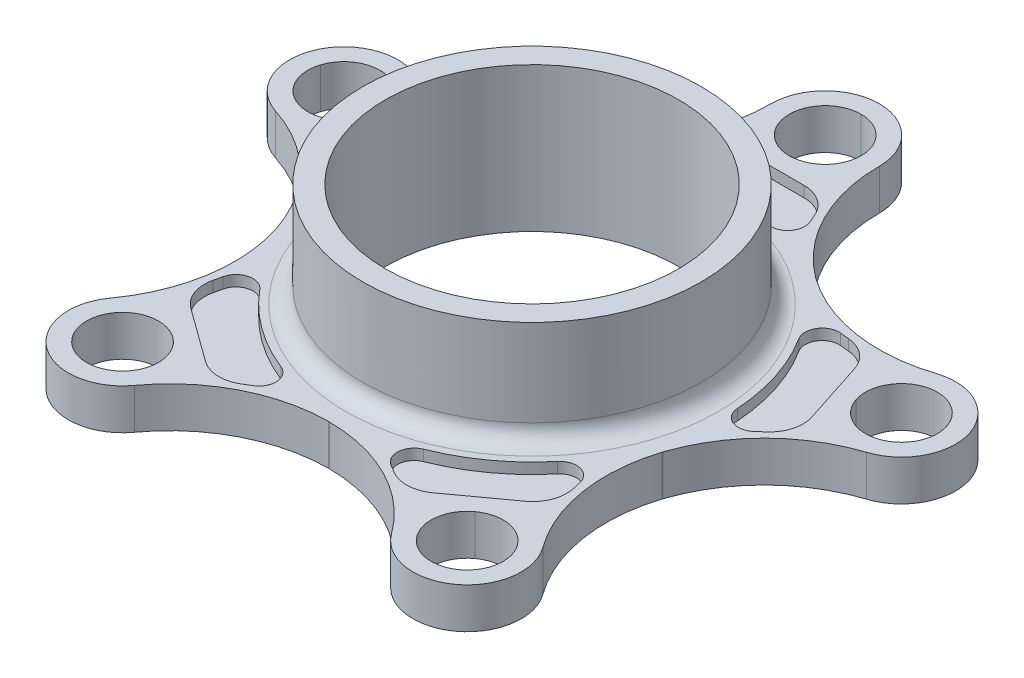
SolidWorks part; units mm, degrees
ref_plane "Front Plane" through (0, 0, 0) normal (0, 0, 1) x (1, 0, 0)
ref_plane "Top Plane" through (0, 0, 0) normal (0, 1, 0) x (1, 0, 0)
ref_plane "Right Plane" through (0, 0, 0) normal (1, 0, 0) x (0, 0, -1)
sketch "Sketch1" plane through (0, 0, 0) normal (0, 1, 0) x (1, 0, 0)
  circle A0 centre (0, 0) radius 31.75
  dimension "D1" = 63.5
extrude "MiddleCircleExtrude" add sketch "Sketch1" along normal blind 19.4945
sketch "Sketch2" plane through (0, 0, 0) normal (0, -1, 0) x (1, 0, 0)
  circle A0 centre (0, 0) radius 80
  dimension "D1" = 160
extrude "StarfishExtrude" add sketch "Sketch2" along normal blind 7.62
sketch "Sketch3" plane through (0, 19.4945, 0) normal (0, 1, 0) x (1, 0, 0)
  circle A0 centre (0, 0) radius 27.5
  dimension "D1" = 55
extrude "CenterHoleCut" cut sketch "Sketch3" against normal through all
sketch "Sketch4" plane through (0, 0, 0) normal (0, 1, 0) x (1, 0, 0)
  circle A0 centre (0, 55) radius 6.75
  circle A1 centre (52.3081, 16.9959) radius 6.75
  circle A2 centre (32.3282, -44.4959) radius 6.75
  circle A3 centre (-32.3282, -44.4959) radius 6.75
  circle A4 centre (-52.3081, 16.9959) radius 6.75
  point P14 (0, 0)
  dimension "D1" = 13.5
  dimension "D2" = 55
  dimension "D3" = 5
extrude "OuterHolesCut" cut sketch "Sketch4" against normal through all
sketch "Sketch5" plane through (0, 0, 0) normal (0, 1, 0) x (1, 0, 0)
  circle A0 centre (52.3081, 16.9959) radius 10.16
  circle A1 centre (0, 55) radius 10.16
  circle A2 centre (-52.3081, 16.9959) radius 10.16
  dimension "D1" = 20.32
  dimension "D2" = 20.32
  dimension "D3" = 20.32
sketch "Sketch7" plane through (0, 0, 0) normal (0, 1, 0) x (1, 0, 0)
  line L0 (0, 55) -> (-52.3081, 16.9959) construction
  line L1 (26.1541, 35.998) -> (18.6622, 25.6863) construction
  line L2 (0, 55) -> (52.3081, 16.9959) construction
  line L3 (-26.1541, 35.998) -> (-18.6622, 25.6863) construction
  arc A1 (-10.16, 55) -> (10.16, 55) centre (0, 55) cw
  circle A16 centre (0, 55) radius 10.16 construction
  arc A19 (10.16, 55) -> (22.4081, 30.8421) centre (40.1082, 55) ccw
  arc A21 (-10.16, 55) -> (-22.4081, 30.8421) centre (-40.1082, 55) cw
  circle A31 centre (0, 0) radius 31.75 construction
  arc A44 (49.1685, 26.6587) -> (22.4081, 30.8421) centre (39.914, 55.1411) cw
  arc A45 (49.1685, 26.6587) -> (55.4477, 7.3332) centre (52.3081, 16.9959) cw
  arc A46 (55.4477, 7.3332) -> (36.2571, -11.7806) centre (64.7022, -21.1493) ccw
  arc A47 (40.5478, -38.524) -> (36.2571, -11.7806) centre (64.7764, -20.9209) cw
  arc A48 (40.5478, -38.524) -> (24.1086, -50.4678) centre (32.3282, -44.4959) cw
  arc A49 (24.1086, -50.4678) -> (0, -38.123) centre (-0.1201, -68.071) ccw
  arc A50 (-24.1086, -50.4678) -> (0, -38.123) centre (0.1201, -68.071) cw
  arc A51 (-24.1086, -50.4678) -> (-40.5478, -38.524) centre (-32.3282, -44.4959) cw
  arc A52 (-40.5478, -38.524) -> (-36.2571, -11.7806) centre (-64.7764, -20.9209) ccw
  arc A53 (-55.4477, 7.3332) -> (-36.2571, -11.7806) centre (-64.7022, -21.1493) cw
  arc A54 (-55.4477, 7.3332) -> (-49.1685, 26.6587) centre (-52.3081, 16.9959) cw
  arc A55 (-49.1685, 26.6587) -> (-22.4081, 30.8421) centre (-39.914, 55.1411) ccw
  point P12 (-22.4081, 30.8421)
  point P15 (-10.16, 55)
  point P42 (22.4081, 30.8421)
  point P50 (0, 0)
  dimension "D1" = 5
extrude "StarfishLegsCut" cut sketch "Sketch7" against normal through all flip side to cut
fillet "WallFillet" radius 3.175 1 edges at (0, 0, 31.75)
fillet "Fillet3" radius 12.7 5 edges at (36.2571, -3.81, 11.7806) (0, -3.81, 38.123) (-36.2571, -3.81, 11.7806) (-22.4081, -3.81, -30.8421) (22.4081, -3.81, -30.8421)
sketch "Sketch14" plane through (0, 0, 0) normal (0, 1, 0) x (1, 0, 0)
  line L0 (0, 0) -> (0, 71.5395) construction
  line L1 (-6.1983, 44.844) -> (6.1983, 44.844)
  line L2 (40.7337, 19.7525) -> (44.5645, 7.9626)
  line L3 (31.3732, -32.6362) -> (21.3441, -39.9228)
  line L4 (-21.3441, -39.9228) -> (-31.3732, -32.6362)
  line L5 (-44.5645, 7.9626) -> (-40.7337, 19.7525)
  arc A0 (8.985, 35.1418) -> (12.6824, 39.4855) centre (9.7714, 38.2179) ccw
  arc A1 (-8.985, 35.1418) -> (8.985, 35.1418) centre (0, 0) cw
  arc A2 (12.6824, 39.4855) -> (12.0479, 40.9649) centre (146.3198, 97.6826) cw
  arc A5 (-8.985, 35.1418) -> (-12.6824, 39.4855) centre (-9.7714, 38.2179) cw
  arc A6 (-12.6824, 39.4855) -> (-12.0479, 40.9649) centre (-146.3198, 97.6826) ccw
  arc A40 (12.0479, 40.9649) -> (6.1983, 44.844) centre (6.1983, 38.494) ccw
  arc A41 (-12.0479, 40.9649) -> (-6.1983, 44.844) centre (-6.1983, 38.494) cw
  arc A42 (35.2369, 24.117) -> (40.7337, 19.7525) centre (34.6945, 17.7902) cw
  arc A43 (42.6829, 1.2006) -> (44.5645, 7.9626) centre (38.5253, 6.0003) ccw
  arc A44 (41.4721, 0.14) -> (42.6829, 1.2006) centre (138.1169, -108.9728) cw
  arc A45 (36.1984, 2.3142) -> (41.4721, 0.14) centre (39.3669, 2.5168) ccw
  arc A46 (30.6454, 19.4046) -> (36.1984, 2.3142) centre (0, 0) cw
  arc A47 (30.6454, 19.4046) -> (33.6339, 24.2634) centre (33.3278, 21.1032) cw
  arc A48 (33.6339, 24.2634) -> (35.2369, 24.117) centre (47.6863, 169.3439) ccw
  arc A49 (33.8255, -26.0597) -> (31.3732, -32.6362) centre (27.6407, -27.499) cw
  arc A50 (14.3316, -40.2228) -> (21.3441, -39.9228) centre (17.6116, -34.7855) ccw
  arc A51 (12.9488, -39.399) -> (14.3316, -40.2228) centre (-60.9588, -165.0315) cw
  arc A52 (13.3869, -33.7116) -> (12.9488, -39.399) centre (14.5587, -36.6624) ccw
  arc A53 (27.9248, -23.1491) -> (13.3869, -33.7116) centre (0, 0) cw
  arc A54 (27.9248, -23.1491) -> (33.4693, -24.49) centre (30.3692, -25.1754) cw
  arc A55 (33.4693, -24.49) -> (33.8255, -26.0597) centre (175.7915, 6.9777) ccw
  arc A56 (-14.3316, -40.2228) -> (-21.3441, -39.9228) centre (-17.6116, -34.7855) cw
  arc A57 (-33.8255, -26.0597) -> (-31.3732, -32.6362) centre (-27.6407, -27.499) ccw
  arc A58 (-33.4693, -24.49) -> (-33.8255, -26.0597) centre (-175.7915, 6.9777) cw
  arc A59 (-27.9248, -23.1491) -> (-33.4693, -24.49) centre (-30.3692, -25.1754) ccw
  arc A60 (-13.3869, -33.7116) -> (-27.9248, -23.1491) centre (0, 0) cw
  arc A61 (-13.3869, -33.7116) -> (-12.9488, -39.399) centre (-14.5587, -36.6624) cw
  arc A62 (-12.9488, -39.399) -> (-14.3316, -40.2228) centre (60.9588, -165.0315) ccw
  arc A63 (-42.6829, 1.2006) -> (-44.5645, 7.9626) centre (-38.5253, 6.0003) cw
  arc A64 (-35.2369, 24.117) -> (-40.7337, 19.7525) centre (-34.6945, 17.7902) ccw
  arc A65 (-33.6339, 24.2634) -> (-35.2369, 24.117) centre (-47.6863, 169.3439) cw
  arc A66 (-30.6454, 19.4046) -> (-33.6339, 24.2634) centre (-33.3278, 21.1032) ccw
  arc A67 (-36.1984, 2.3142) -> (-30.6454, 19.4046) centre (0, 0) cw
  arc A68 (-36.1984, 2.3142) -> (-41.4721, 0.14) centre (-39.3669, 2.5168) cw
  arc A69 (-41.4721, 0.14) -> (-42.6829, 1.2006) centre (-138.1169, -108.9728) ccw
  point P9 (10.4745, 44.844)
  point P32 (0.6385, 0.6404)
  point P33 (0, 0)
  point P36 (-10.4745, 44.844)
  point P80 (0, 0)
  point P83 (0, 0)
  dimension "D1" = 3.175
  dimension "D3" = 6.35
  dimension "D2" = 5
extrude "TopOfFloorCut" cut sketch "Sketch14" against normal blind 2.032 separate body
sketch "Sketch15" plane through (0, 0, 0) normal (1, 0, 0) x (0, 0, -1)
  line L0 (0, 0) -> (0, 36.5807) construction
  line L1 (0, 0) -> (3.6952, 42.2366) construction
  line L2 (0, 0) -> (0, -23.7648) construction
  dimension "D1" = 5
sketch "Sketch26" plane through (0, 0, 0) normal (0, 1, 0) x (1, 0, 0)
  line L0 (0, 78.7283) -> (0, 17.5539)
  line L1 (74.8751, 24.3284) -> (16.6947, 5.4244)
  line L2 (46.2754, -63.6926) -> (10.3179, -14.2014)
  line L3 (-46.2754, -63.6926) -> (-10.3179, -14.2014)
  line L4 (-74.8751, 24.3284) -> (-16.6947, 5.4244)
  point P2 (0, 0)
  point P3 (0, 0)
  point P13 (0, 0)
  dimension "D1" = 5
split line "Split Line25"
sketch "Sketch28" plane through (0, -7.62, 0) normal (0, -1, 0) x (1, 0, 0)
  line L0 (5.092, -44.844) -> (-5.092, -44.844)
  line L5 (0, -44.844) -> (0, -36.4409) construction
  line L6 (0, -78.7283) -> (0, -17.5539) construction
  line L7 (-41.0756, -18.7004) -> (-44.2227, -9.0147)
  line L8 (-30.4782, 33.2865) -> (-22.2391, 39.2725)
  line L9 (22.2391, 39.2725) -> (30.4782, 33.2865)
  line L10 (44.2227, -9.0147) -> (41.0756, -18.7004)
  arc A0 (-7.7091, -35.4472) -> (-11.3245, -39.7834) centre (-8.4006, -38.546) ccw
  arc A1 (0, -36.4409) -> (-7.7091, -35.4472) centre (1.5705, 6.1424) cw
  arc A2 (-11.3245, -39.7834) -> (-11.279, -39.9235) centre (-12.1089, -40.1153) cw
  arc A5 (-11.279, -39.9235) -> (-5.092, -44.844) centre (-5.092, -38.494) ccw
  arc A35 (0, -36.4409) -> (7.7091, -35.4472) centre (-1.5705, 6.1424) ccw
  arc A36 (7.7091, -35.4472) -> (11.3245, -39.7834) centre (8.4006, -38.546) cw
  arc A37 (11.279, -39.9235) -> (5.092, -44.844) centre (5.092, -38.494) cw
  arc A38 (11.3245, -39.7834) -> (11.279, -39.9235) centre (12.1089, -40.1153) ccw
  arc A39 (-34.3368, -23.064) -> (-34.4841, -23.064) centre (-34.4101, -23.9126) ccw
  arc A40 (-34.4841, -23.064) -> (-41.0756, -18.7004) centre (-35.0364, -16.7381) cw
  arc A41 (-41.455, -1.6101) -> (-44.2227, -9.0147) centre (-38.1835, -7.0525) ccw
  arc A42 (-41.3357, -1.5235) -> (-41.455, -1.6101) centre (-41.8938, -0.8801) cw
  arc A43 (-36.0945, -3.622) -> (-41.3357, -1.5235) centre (-39.2553, -3.922) ccw
  arc A44 (-34.6574, -11.2609) -> (-36.0945, -3.622) centre (6.327, 0.4045) cw
  arc A45 (-34.6574, -11.2609) -> (-31.33, -18.2856) centre (5.3564, 3.3917) ccw
  arc A46 (-31.33, -18.2856) -> (-34.3368, -23.064) centre (-34.0635, -19.9008) cw
  arc A47 (-32.5458, 25.529) -> (-32.5914, 25.6692) centre (-33.3755, 25.3365) ccw
  arc A48 (-32.5914, 25.6692) -> (-30.4782, 33.2865) centre (-26.7457, 28.1492) cw
  arc A49 (-14.3415, 38.9285) -> (-22.2391, 39.2725) centre (-18.5066, 34.1353) ccw
  arc A50 (-14.2223, 38.8418) -> (-14.3415, 38.9285) centre (-13.7829, 39.5714) cw
  arc A51 (-14.5985, 33.2087) -> (-14.2223, 38.8418) centre (-15.8606, 36.1221) ccw
  arc A52 (-21.4194, 29.4813) -> (-14.5985, 33.2087) centre (2.3399, -5.8924) cw
  arc A53 (-21.4194, 29.4813) -> (-27.0722, 24.146) centre (4.8809, -4.0462) ccw
  arc A54 (-27.0722, 24.146) -> (-32.5458, 25.529) centre (-29.4529, 26.2466) cw
  arc A55 (14.2223, 38.8418) -> (14.3415, 38.9285) centre (13.7829, 39.5714) ccw
  arc A56 (14.3415, 38.9285) -> (22.2391, 39.2725) centre (18.5066, 34.1353) cw
  arc A57 (32.5914, 25.6692) -> (30.4782, 33.2865) centre (26.7457, 28.1492) ccw
  arc A58 (32.5458, 25.529) -> (32.5914, 25.6692) centre (33.3755, 25.3365) cw
  arc A59 (27.0722, 24.146) -> (32.5458, 25.529) centre (29.4529, 26.2466) ccw
  arc A60 (21.4194, 29.4813) -> (27.0722, 24.146) centre (-4.8809, -4.0462) cw
  arc A61 (21.4194, 29.4813) -> (14.5985, 33.2087) centre (-2.3399, -5.8924) ccw
  arc A62 (14.5985, 33.2087) -> (14.2223, 38.8418) centre (15.8606, 36.1221) cw
  arc A63 (41.3357, -1.5235) -> (41.455, -1.6101) centre (41.8938, -0.8801) ccw
  arc A64 (41.455, -1.6101) -> (44.2227, -9.0147) centre (38.1835, -7.0525) cw
  arc A65 (34.4841, -23.064) -> (41.0756, -18.7004) centre (35.0364, -16.7381) ccw
  arc A66 (34.3368, -23.064) -> (34.4841, -23.064) centre (34.4101, -23.9126) cw
  arc A67 (31.33, -18.2856) -> (34.3368, -23.064) centre (34.0635, -19.9008) ccw
  arc A68 (34.6574, -11.2609) -> (31.33, -18.2856) centre (-5.3564, 3.3917) cw
  arc A69 (34.6574, -11.2609) -> (36.0945, -3.622) centre (-6.327, 0.4045) ccw
  arc A70 (36.0945, -3.622) -> (41.3357, -1.5235) centre (39.2553, -3.922) cw
  point P91 (0, 0)
  dimension "D1" = 3.175
  dimension "D2" = 6.35
  dimension "D3" = 5
extrude "BottomOfFloorCut" cut sketch "Sketch28" against normal blind 2.032
ref_axis "Axis1" through (0, 0, 0) along (0, 0.9962, -0.0872)
sketch "Sketch30" plane through (0, -7.62, 0) normal (0, -1, 0) x (1, 0, 0)
  line L0 (0, 0) -> (52.1509, 0) construction
sketch "Sketch32" plane through (0, 0, 0) normal (0, 0, 1) x (1, 0, 0)
  line L0 (0, -7.62) -> (30.5533, -2.2326)
  line L1 (0, -7.62) -> (52.1509, -7.62) construction
  dimension "D1" = 10
sketch "Sketch24" plane through (0, 0, 0) normal (0, 1, 0) x (1, 0, 0)
  line L0 (-49.1685, 26.6587) -> (-55.4477, 7.3332) construction
  line L1 (10.16, 55) -> (-10.16, 55) construction
  line L2 (49.1685, 26.6587) -> (55.4477, 7.3332) construction
  line L3 (40.5478, -38.524) -> (24.1086, -50.4678) construction
  line L4 (-40.5478, -38.524) -> (-24.1086, -50.4678) construction
  circle A0 centre (52.3081, 16.9959) radius 10.16 construction
sketch "Sketch25" plane through (0, 0, 0) normal (0, 1, 0) x (1, 0, 0)
  line L0 (0, 40.4337) -> (0, 69.5663)
  line L1 (37.5882, 12.2132) -> (67.028, 21.7787)
  line L2 (27.3557, -37.6519) -> (42.0755, -57.9119)
  line L3 (-26.9625, -37.1107) -> (-41.5402, -57.1752)
  line L4 (-26.7282, 8.6845) -> (-77.888, 25.3074)
  line L5 (49.1685, 26.6587) -> (55.4477, 7.3332) construction
  line L6 (40.5478, -38.524) -> (24.1086, -50.4678) construction
  line L7 (-40.5478, -38.524) -> (-24.1086, -50.4678) construction
  line L8 (-49.1685, 26.6587) -> (-55.4477, 7.3332) construction
  line L9 (32.3282, -44.4959) -> (34.244, -47.1328)
  line L10 (-31.0734, -42.7688) -> (-32.3282, -44.4959)
  point P2 (0, 0)
ref_plane "Plane4" through (-52.3081, 0, -16.9959) normal (0.9511, 0, 0.309) x (0.309, 0, -0.9511)
ref_plane "Plane3" through (0, 0, -55) normal (0, 0, 1) x (1, 0, 0)
sketch "Sketch17" plane through (0, 0, -55) normal (0, 0, 1) x (1, 0, 0)
  line L0 (3.7802, 0) -> (10.16, 0)
